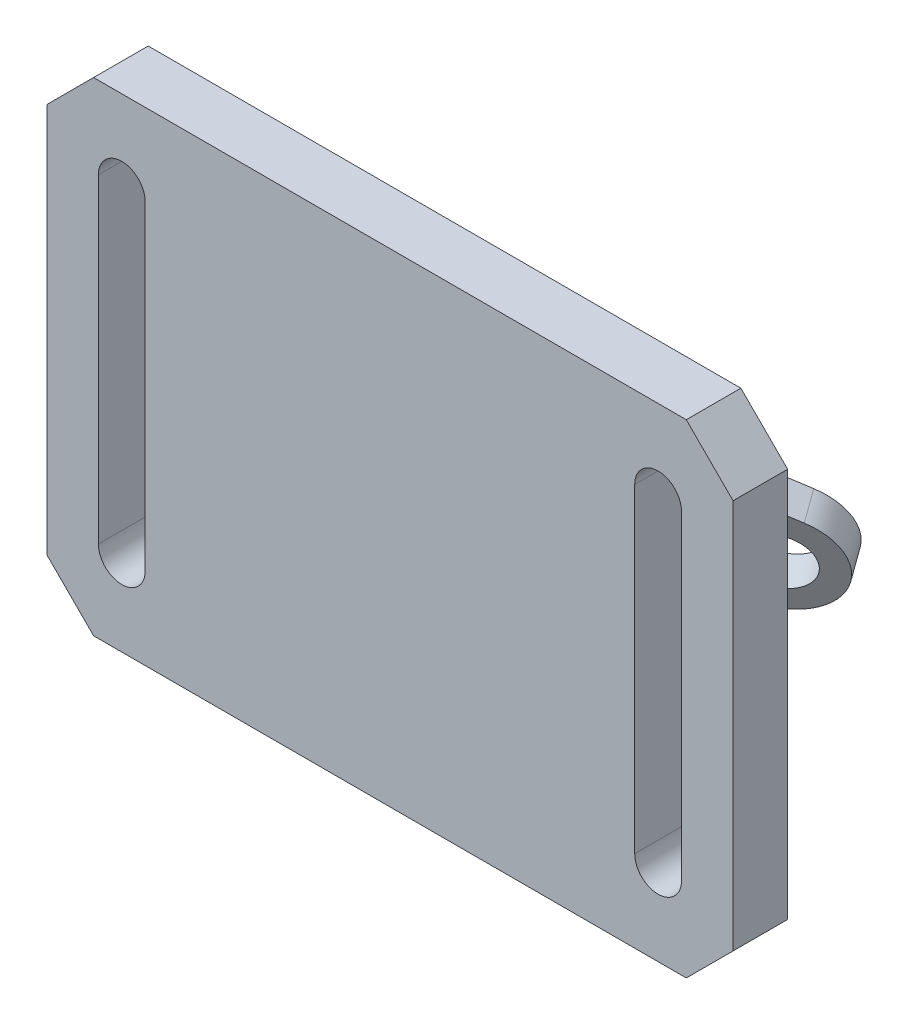
SolidWorks part; units mm, degrees
material "Alloy Steel"
ref_plane "Front Plane" through (0, 0, 0) normal (0, 0, 1) x (1, 0, 0)
ref_plane "Top Plane" through (0, 0, 0) normal (0, 1, 0) x (1, 0, 0)
ref_plane "Right Plane" through (0, 0, 0) normal (1, 0, 0) x (0, 0, -1)
sketch "Sketch1" plane through (0, 0, 0) normal (0, 0, 1) x (1, 0, 0)
  line L0 (-44, 25) -> (-38, 31)
  line L1 (-38, 31) -> (38, 31)
  line L2 (-44, 25) -> (-44, -25)
  line L3 (-38, -31) -> (38, -31)
  line L4 (44, 25) -> (44, -25)
  line L5 (-44, 31) -> (44, -31) construction
  line L6 (-44, -31) -> (44, 31) construction
  line L7 (38, 31) -> (44, 25)
  line L8 (38, -31) -> (44, -25)
  line L9 (-44, -25) -> (-38, -31)
  line L10 (-34.3856, 20.5) -> (-34.3856, -20.5) construction
  line L11 (-31.3856, 20.5) -> (-31.3856, -20.5)
  line L12 (-37.3856, 20.5) -> (-37.3856, -20.5)
  line L13 (0, 31) -> (0, -31) construction
  line L14 (34.3856, 20.5) -> (34.3856, -20.5) construction
  line L15 (31.3856, 20.5) -> (31.3856, -20.5)
  line L16 (37.3856, 20.5) -> (37.3856, -20.5)
  arc A0 (-31.3856, 20.5) -> (-37.3856, 20.5) centre (-34.3856, 20.5) ccw
  arc A1 (-37.3856, -20.5) -> (-31.3856, -20.5) centre (-34.3856, -20.5) ccw
  arc A2 (31.3856, 20.5) -> (37.3856, 20.5) centre (34.3856, 20.5) cw
  arc A3 (37.3856, -20.5) -> (31.3856, -20.5) centre (34.3856, -20.5) cw
  point P0 (0, 0)
  point P16 (-34.3856, 0)
  point P21 (0, -31)
  point P26 (34.3856, 0)
  dimension "D1" = 62
  dimension "D2" = 88
  dimension "D3" = 6
  dimension "D4" = 45
  dimension "D5" = 6
  dimension "D6" = 45
  dimension "D7" = 6
  dimension "D8" = 45
  dimension "D9" = 6
  dimension "D10" = 45
  dimension "D11" = 6
  dimension "D12" = 41
  dimension "D13" = 8
extrude "Boss-Extrude1" add sketch "Sketch1" along normal blind 7
ref_axis "Axis1" through (0, 0, -0.35) along (0, 0, 1)
sketch "Sketch3" plane through (0, 0, 0) normal (0, 0, -1) x (-1, 0, 0)
  line L0 (37.3856, 20.5) -> (37.3856, -20.5) construction
  line L1 (37.3856, 20.5) -> (37.3856, -20.5)
  line L2 (31.3856, 20.5) -> (37.3856, 20.5) construction
  line L3 (34.3856, 23.5) -> (34.3856, 20.5) construction
  arc A0 (37.3856, 20.5) -> (31.3856, 20.5) centre (34.3856, 20.5) ccw construction
ref_axis "Axis2" through (-34.3856, 20.5, 0) along (0, 0, 1)
ref_plane "Plane2" through (0, 0, 0) normal (-0.5121, -0.8589, 0) x (-0.8589, 0.5121, 0)
sketch "Sketch2" plane through (0, 0, 0) normal (-0.5121, -0.8589, 0) x (-0.8589, 0.5121, 0)
  line L3 (20.0327, 0) -> (-14.3001, 0)
  line L5 (-14.3001, 24.9443) -> (20.0327, 0)
  line L8 (-14.3001, 0) -> (-14.3001, 20)
  line L9 (-14.3001, 20) -> (-26.4354, 28.8168)
  line L10 (-26.4354, 28.8168) -> (-24.0842, 32.0528)
  line L11 (-14.3001, 24.9443) -> (-24.0842, 32.0528)
  dimension "D1" = 20
  dimension "D2" = 36
  dimension "D3" = 20
  dimension "D4" = 4
  dimension "D5" = 15
extrude "Boss-Extrude2" add sketch "Sketch2" along normal mid plane 14
fillet "Fillet1" radius 7 2 edges at (25.2811, -6.9225, -30.4348) (18.112, -18.9476, -30.4348)
sketch "Sketch6" plane through (-5.9448, 3.5442, -9.5261) normal (-0.5049, 0.301, -0.809) x (-0.8632, -0.176, 0.4732)
  line L0 (-29.3699, -12.9479) -> (-21.0646, -24.2182) construction
  line L1 (-30.8524, -22.7357) -> (-25.2172, -18.583) construction
  circle A0 centre (-25.2172, -18.583) radius 4
  dimension "D2" = 8
  dimension "D1" = 14
extrude "Cut-Extrude1" cut sketch "Sketch6" against normal up to next
